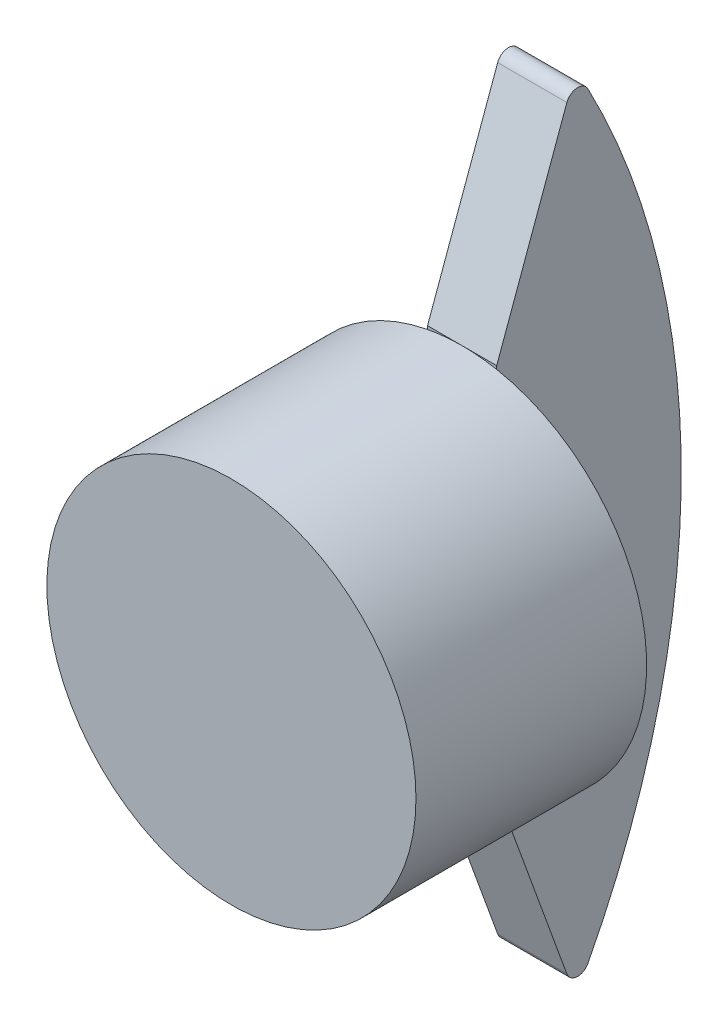
SolidWorks part; units mm, degrees
ref_plane "Front" through (0, 0, 0) normal (0, 0, 1) x (1, 0, 0)
ref_plane "Top" through (0, 0, 0) normal (0, 1, 0) x (1, 0, 0)
ref_plane "Right" through (0, 0, 0) normal (1, 0, 0) x (0, 0, -1)
sketch "ｽｹｯﾁ1" plane through (0, 0, 0) normal (0, 0, 1) x (1, 0, 0)
  circle A0 centre (0, 0) radius 8
  dimension "D1" = 16
extrude "ﾎﾞｽ - 押し出し1" add sketch "ｽｹｯﾁ1" along normal blind 10
sketch "ｽｹｯﾁ2" plane through (0, 0, 0) normal (1, 0, 0) x (0, 0, -1)
  line L0 (0, -8) -> (0, 8)
  line L1 (0, 8) -> (3.4202, 17.3969)
  line L2 (0, -8) -> (3.4202, -17.3969)
  arc A0 (3.4202, -17.3969) -> (3.4202, 17.3969) centre (-27.3321, 0) ccw
  point P7 (8, 0)
  dimension "D1" = 20
  dimension "D2" = 20
  dimension "D3" = 10
  dimension "D4" = 10
  dimension "D5" = 8
extrude "ﾎﾞｽ - 押し出し2" add sketch "ｽｹｯﾁ2" along normal blind 1.5 and the other way blind 1.5
fillet "ﾌｨﾚｯﾄ1" radius 0.5 2 edges at (0, -17.3969, -3.4202) (0, 17.3969, -3.4202)
sketch "ｽｹｯﾁ4" plane through (-1.5, 0, 0) normal (-1, 0, 0) x (0, 0, 1)
  arc A0 (-3.954, 16.4176) -> (-3.954, -16.4176) centre (27.3321, 0) ccw construction
  point P0 (-8, 0)
ref_plane "平面1" through (0, 0, -8) normal (0, 0, -1) x (-1, 0, 0)
sketch "ｽｹｯﾁ5" plane through (0, 0, -8) normal (0, 0, -1) x (-1, 0, 0)
  line L0 (1.5, 0) -> (-1.5, 0)
  dimension "D1" = 3
